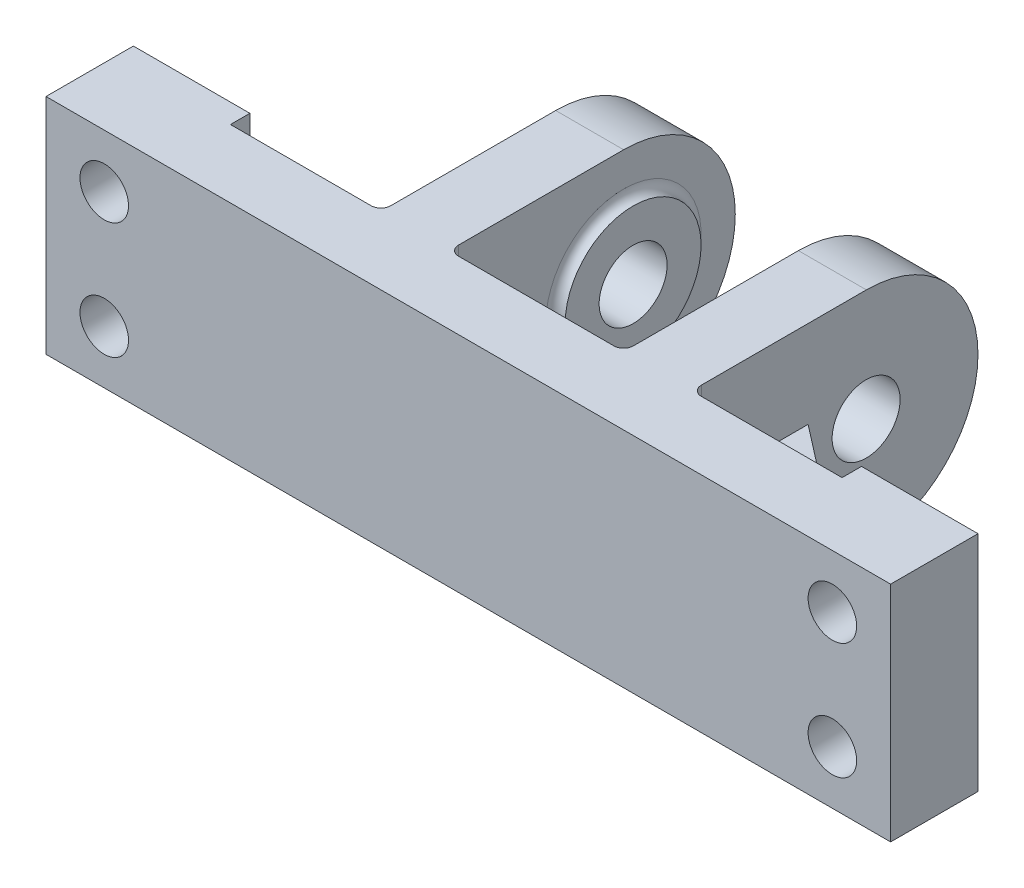
SolidWorks part; units mm, degrees
ref_plane "Front Plane" through (0, 0, 0) normal (0, 0, 1) x (1, 0, 0)
ref_plane "Top Plane" through (0, 0, 0) normal (0, 1, 0) x (1, 0, 0)
ref_plane "Right Plane" through (0, 0, 0) normal (1, 0, 0) x (0, 0, -1)
sketch "Sketch1" plane through (0, 0, 0) normal (0, 0, 1) x (1, 0, 0)
  line L1 (-87, 23) -> (87, 23)
  line L2 (-87, 23) -> (-87, -23)
  line L3 (-87, -23) -> (87, -23)
  line L4 (87, 23) -> (87, -23)
  line L5 (-87, 23) -> (87, -23) construction
  line L6 (-87, -23) -> (87, 23) construction
  point P0 (0, 0)
  dimension "D1" = 174
  dimension "D2" = 46
extrude "Boss-Extrude1" add sketch "Sketch1" along normal blind 18
sketch "Sketch2" plane through (0, 0, 0) normal (0, 0, -1) x (-1, 0, 0)
  line L0 (87, -23) -> (-87, -23) construction
  line L1 (-63, 23) -> (63, 23)
  line L2 (-63, 23) -> (-63, -23)
  line L3 (-63, -23) -> (63, -23)
  line L4 (63, 23) -> (63, -23)
  line L5 (-63, 23) -> (63, -23) construction
  line L6 (-63, -23) -> (63, 23) construction
  point P0 (0, 0)
  dimension "D1" = 126
extrude "Cut-Extrude1" cut sketch "Sketch2" against normal blind 4
sketch "Sketch3" plane through (0, 0, 0) normal (0, 0, -1) x (-1, 0, 0)
  line L0 (0, 0) -> (157.5369, 0) construction
  line L1 (75, 23) -> (75, -42.6503) construction
  line L2 (63, 23) -> (87, 23) construction
  line L3 (0, 46.6417) -> (0, -59.5261) construction
  circle A0 centre (75, 12) radius 5
  circle A1 centre (75, -12) radius 5
  circle A2 centre (-75, -12) radius 5
  circle A3 centre (-75, 12) radius 5
  dimension "D1" = 10
  dimension "D2" = 12
extrude "Cut-Extrude2" cut sketch "Sketch3" against normal through all
ref_plane "Plane1" through (-32, 0, 0) normal (-1, 0, 0) x (0, 0, 1)
sketch "Sketch4" plane through (-32, 0, 0) normal (-1, 0, 0) x (0, 0, 1)
  line L0 (4, 23) -> (-32, 23)
  line L1 (4, -23) -> (-32, -23)
  line L6 (0, 23) -> (0, -23)
  line L7 (4, 23) -> (0, 23)
  line L8 (4, -23) -> (4, 23)
  line L9 (0, -23) -> (4, -23)
  line L12 (4, -23) -> (4, 23)
  arc A0 (-32, 23) -> (-32, -23) centre (-32, 0) ccw
  dimension "D1" = 36
  dimension "D2" = 0
extrude "Boss-Extrude3" add sketch "Sketch4" against normal blind 14
sketch "Sketch6" plane through (-18, 0, 0) normal (1, 0, 0) x (0, 0, -1)
  circle A0 centre (31.9528, 0) radius 14
  dimension "D1" = 28
extrude "Boss-Extrude5" add sketch "Sketch6" along normal blind 2
sketch "Sketch7" plane through (-16, 0, 0) normal (1, 0, 0) x (0, 0, -1)
  circle A0 centre (31.9528, 0) radius 7
  dimension "D1" = 14
extrude "Cut-Extrude3" cut sketch "Sketch7" against normal up to next
sketch "Sketch9" plane through (0, 0, 0) normal (0, 1, 0) x (1, 0, 0)
  line L0 (-32, 20) -> (-63, -4)
  line L1 (-32, -4) -> (-32, 32) construction
  line L2 (-32, 20) -> (-32, -4)
  line L3 (-32, 9.9) -> (-32, -9.9) construction
  line L4 (-32, -4) -> (-63, -4)
  dimension "D1" = 12
extrude "Boss-Extrude7" add sketch "Sketch9" along normal blind 5 and the other way blind 5
mirror "Mirror1" about plane through (0, 0, 0) normal (1, 0, 0) of "Cut-Extrude3", "Boss-Extrude3", "Boss-Extrude5", "Boss-Extrude7"
fillet "Fillet1" radius 2 6 edges at (-18, 0, 4) (-32, -14, 4) (-32, 14, 4) (18, 0, 4) (32, -14, 4) (32, 14, 4)
fillet "Fillet2" radius 2 2 edges at (18, 0, -45.9528) (-18, 0, -17.9528)
